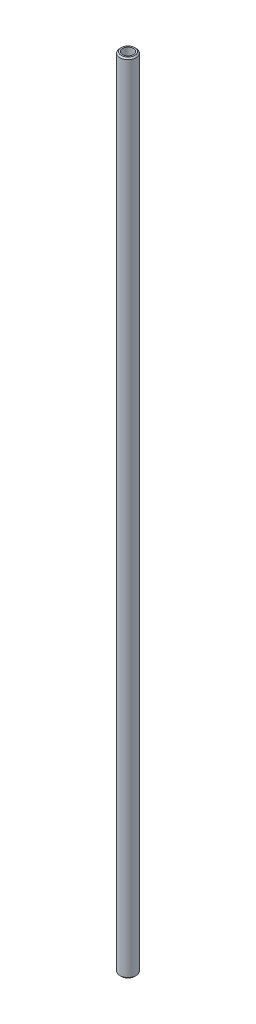
SolidWorks part; units mm, degrees
ref_plane "Plan de face" through (0, 0, 0) normal (0, 0, 1) x (1, 0, 0)
ref_plane "Plan de dessus" through (0, 0, 0) normal (0, 1, 0) x (1, 0, 0)
ref_plane "Plan de droite" through (0, 0, 0) normal (1, 0, 0) x (0, 0, -1)
sketch "Esquisse2" plane through (0, 0, 0) normal (0, 1, 0) x (1, 0, 0)
  line L0 (4071.8961, -760.5117) -> (4089.3784, -787.9092) construction
  circle A0 centre (4080.6372, -774.2105) radius 3
  circle A1 centre (4080.6372, -774.2105) radius 2
  dimension "D1" = 6
  dimension "D2" = 4
extrude "Boss.-Extru.1" add sketch "Esquisse2" along normal blind 295
chamfer "Chanfrein1" distance 0.5 angle 45 2 edges at (4080.6372, 295, 777.2105) (4080.6372, 0, 777.2105)
